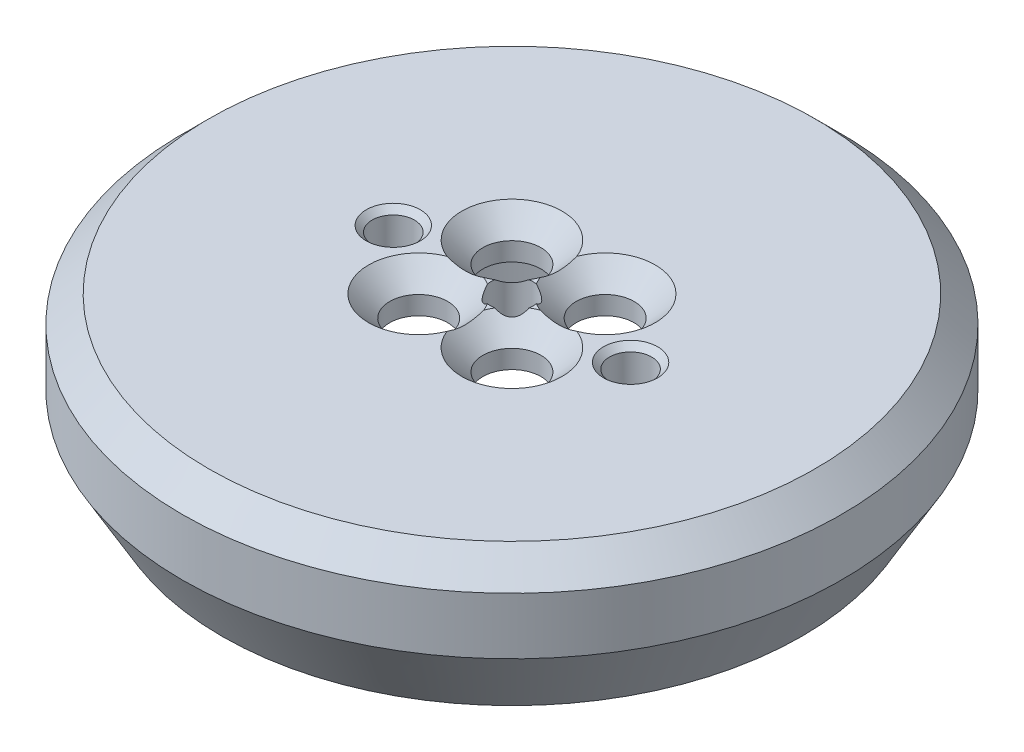
SolidWorks part; units mm, degrees
ref_plane "Front Plane" through (0, 0, 0) normal (0, 0, 1) x (1, 0, 0)
ref_plane "Top Plane" through (0, 0, 0) normal (0, 1, 0) x (1, 0, 0)
ref_plane "Right Plane" through (0, 0, 0) normal (1, 0, 0) x (0, 0, -1)
sketch "Sketch1" plane through (0, 0, 0) normal (0, 1, 0) x (1, 0, 0)
  circle A0 centre (0, 0) radius 12.5
  dimension "D1" = 25
extrude "Boss-Extrude1" add sketch "Sketch1" along normal blind 1.5
sketch "Sketch2" plane through (0, 1.5, 0) normal (0, 1, 0) x (1, 0, 0)
  circle A0 centre (0, 0) radius 0.8
  dimension "D1" = 1.6
extrude "Cut-Extrude1" cut sketch "Sketch2" against normal through all both and the other way through all
hole_wizard "CSK for M2 Flat Head Machine Screw1" positions "Sketch3" profile "Sketch4" countersink size "M2" standard "ANSI Metric"
sketch "Sketch3" plane through (0, 1.5, 0) normal (0, 1, 0) x (1, 0, 0)
  line L1 (-1.7678, 1.7678) -> (1.7678, 1.7678)
  line L2 (-1.7678, 1.7678) -> (-1.7678, -1.7678)
  line L3 (-1.7678, -1.7678) -> (1.7678, -1.7678)
  line L4 (1.7678, 1.7678) -> (1.7678, -1.7678)
  line L5 (-1.7678, 1.7678) -> (1.7678, -1.7678) construction
  point P0 (-1.7678, 1.7678)
  point P2 (1.7678, 1.7678)
  point P4 (1.7678, -1.7678)
  point P6 (-1.7678, -1.7678)
  point P120 (0, 0)
  dimension "D1" = 5
sketch "Sketch4" plane through (-1.7678, 1.5, -1.7678) normal (1, 0, 0) x (0, 0, 1)
  line L0 (0, 0) -> (0, 5.6609)
  line L1 (0, 5.6609) -> (1.1, 5)
  line L2 (1.1, 5) -> (1.1, 0.8)
  line L3 (1.1, 0.8) -> (1.9, 0)
  line L5 (1.9, 0) -> (0, 0)
  line L6 (-1.1, 0.8) -> (-1.9, 0) construction
  line L10 (0, 5.6609) -> (-1.1, 5) construction
  line L11 (0, -6.35) -> (0, 107.95) construction
  dimension "Hole Dia." = 2.2
  dimension "Hole Depth" = 5
  dimension "Near C'Sink Dia." = 3.8
  dimension "Near C'Sink Angle" = 90
  dimension "Drill Angle" = 118
sketch "Sketch6" plane through (0, 0, 0) normal (0, 0, 1) x (1, 0, 0)
  line L0 (-12.5, 0) -> (-12.5, -1.25)
  line L1 (-12.5, -1.25) -> (-7.2, -1.25)
  line L2 (-7.2, -1.25) -> (-5, 0)
  line L3 (-5, 0) -> (-12.5, 0)
  line L4 (0, 0) -> (0, -5.6432) construction
  dimension "D1" = 1.25
  dimension "D2" = 5
  dimension "D3" = 7.2
revolve "Revolve1" add sketch "Sketch6" angle 360 about L4
sketch "Sketch7" plane through (0, -1.25, 0) normal (0, -1, 0) x (1, 0, 0)
  circle A0 centre (0, 0) radius 7.2 construction
  circle A1 centre (0, 0) radius 12.5
  circle A2 centre (0, 0) radius 12.5
  circle A3 centre (0, 0) radius 7.2
  dimension "D1" = 0
extrude "Boss-Extrude2" add sketch "Sketch7" along normal blind 3
sketch "Sketch11" plane through (0, 1.5, 0) normal (0, 1, 0) x (1, 0, 0)
  line L0 (0, 0) -> (-3.2481, 0) construction
  line L1 (-7.25, 5.1678) -> (-7.25, -5.1678)
  line L2 (-7.25, -5.1678) -> (7.25, -5.1678)
  line L3 (7.25, -5.1678) -> (7.25, 5.1678)
  line L4 (7.25, 5.1678) -> (-7.25, 5.1678)
  line L5 (-7.25, 5.1678) -> (7.25, -5.1678) construction
  line L6 (-1.7678, -3.6678) -> (-1.7678, -5.1678) construction
  line L7 (-0.6889, -3.6678) -> (-2.8466, -3.6678) construction
  circle A0 centre (0, 0) radius 10
  arc A4 (-2.4642, 0) -> (0, -2.4642) centre (-1.7678, -1.7678) ccw construction
  dimension "D1" = 1.5
  dimension "D3" = 20
  dimension "D2" = 14.5
extrude "Boss-Extrude3" [suppressed] add sketch "Sketch11" along normal blind 3
fillet "Fillet2" [suppressed] radius 5
fillet "Fillet3" [suppressed] radius 1
fillet "Fillet1" radius 1 2 edges at (0, 0, 5) (0, -1.25, 7.2)
loft "Loft2" [suppressed] add
sketch "Sketch14" [suppressed] plane through (0, 4.5, 0) normal (0, 1, 0) x (1, 0, 0)
  circle A0 centre (0, 0) radius 10 construction
  circle A1 centre (0, 0) radius 10
extrude "Cut-Extrude2" [suppressed] cut sketch "Sketch14" against normal through all both and the other way through all
combine bodies "Combine1" [suppressed] operation type add bodies to combine 110 107
chamfer "Chamfer1" distance 1 angle 45 1 edges at (0, 1.5, 12.5)
chamfer "Chamfer2" distance 1 angle 45 1 edges at (0, -4.25, -7.2)
chamfer "Chamfer3" distance 1.5 angle 60 1 edges at (0, -4.25, -12.5) first distance on face at (0, -4.25, -8.2)
hole_wizard "M2x0.4 Tapped Hole1" positions "Sketch8" profile "Sketch9" tap size "M2x0.4" standard "ANSI Metric"
sketch "Sketch8" plane through (0, 1.5, 0) normal (0, 1, 0) x (1, 0, 0)
  line L0 (-4.5, 0) -> (4.5, 0) construction
  point P0 (-4.5, 0)
  point P2 (4.5, 0)
  dimension "D1" = 9
sketch "Sketch9" plane through (-4.5, 1.5, 0) normal (1, 0, 0) x (0, 0, 1)
  line L0 (0, 0) -> (0, 5.6807)
  line L1 (0, 5.6807) -> (0.8, 5.2)
  line L2 (0.8, 5.2) -> (0.8, 0.225)
  line L3 (0.8, 0.225) -> (1.025, 0)
  line L5 (1.025, 0) -> (0, 0)
  line L6 (-0.8, 0.225) -> (-1.025, 0) construction
  line L10 (0, 5.6807) -> (-0.8, 5.2) construction
  line L11 (0, -6.35) -> (0, 107.95) construction
  dimension "Tap Drill Dia." = 1.6
  dimension "Tap Drill Depth" = 5.2
  dimension "Near C'Sink Dia." = 2.05
  dimension "Near C'Sink Angle" = 90
  dimension "Drill Angle" = 118
cosmetic thread "Hole Thread1" parameters "D1"=2.4801, "D2"=2
cosmetic thread "Hole Thread2" parameters "D1"=2.4801, "D2"=2
